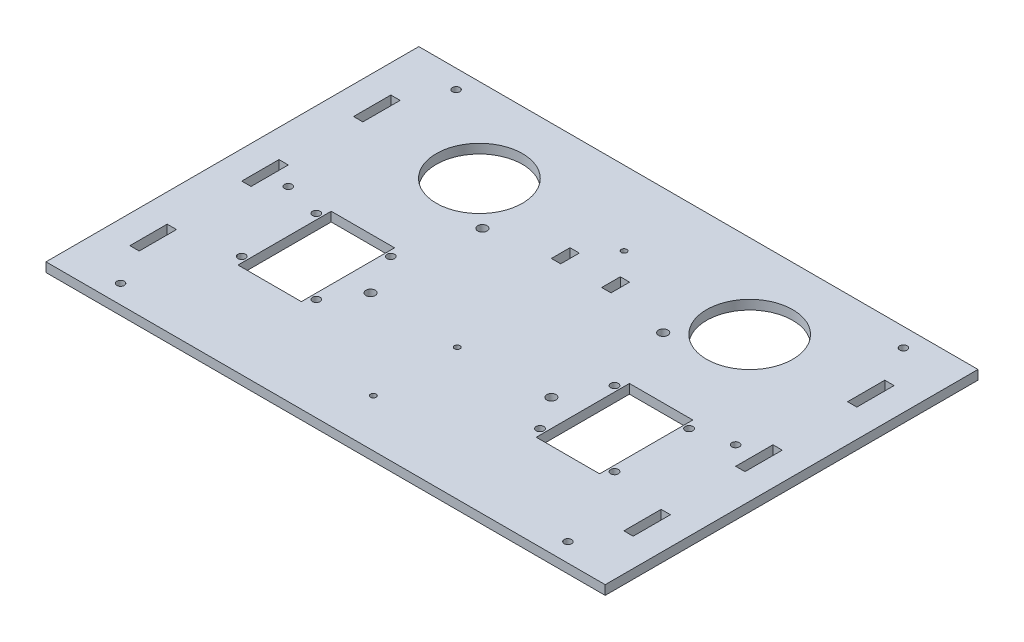
SolidWorks part; units mm, degrees
ref_plane "前基準面" through (0, 0, 0) normal (0, 0, 1) x (1, 0, 0)
ref_plane "上基準面" through (0, 0, 0) normal (0, 1, 0) x (1, 0, 0)
ref_plane "右基準面" through (0, 0, 0) normal (1, 0, 0) x (0, 0, -1)
sketch "草圖1" plane through (0, 0, 0) normal (0, 1, 0) x (1, 0, 0)
  line L0 (-130, 90) -> (130, 90) construction
  line L1 (-150, 100) -> (150, 100)
  line L2 (-150, 100) -> (-150, -100)
  line L3 (-150, -100) -> (150, -100)
  line L5 (0, 100) -> (0, -100) construction
  line L8 (-130, 100) -> (-110, 100) construction
  line L9 (-150, 100) -> (-150, -100) construction
  line L16 (-130, 100) -> (-130, -100) construction
  line L17 (-130, -100) -> (-110, -100) construction
  line L35 (-110, 100) -> (-110, -100) construction
  line L38 (-110, 100) -> (110, 100) construction
  line L41 (-110, 100) -> (-110, 80) construction
  line L50 (-110, 80) -> (110, 80) construction
  line L59 (110, 100) -> (110, 80) construction
  line L65 (-150, -100) -> (150, -100) construction
  line L68 (150, -100) -> (150, 100)
  line L77 (110, 100) -> (130, 100) construction
  line L80 (110, 100) -> (110, -100) construction
  line L83 (110, -100) -> (130, -100) construction
  line L86 (130, 100) -> (130, -100) construction
  line L89 (110, -100) -> (-110, -100) construction
  line L92 (110, -100) -> (110, -80) construction
  line L93 (-150, 100) -> (150, 100) construction
  line L108 (110, -80) -> (-110, -80) construction
  line L109 (-110, -100) -> (-110, -80) construction
  line L110 (130, -70) -> (135, -70)
  line L111 (-120, 100) -> (-120, -100) construction
  line L112 (-130, -90) -> (130, -90) construction
  line L113 (120, -100) -> (120, 100) construction
  line L114 (-130, 70) -> (-135, 70)
  line L115 (-130, 70) -> (-130, 50)
  line L116 (-130, 50) -> (-135, 50)
  line L117 (-135, 70) -> (-135, 50)
  line L118 (-130, 10) -> (-135, 10)
  line L119 (-130, 10) -> (-130, -10)
  line L120 (-130, -10) -> (-135, -10)
  line L121 (-135, 10) -> (-135, -10)
  line L122 (-130, -50) -> (-135, -50)
  line L123 (-130, -50) -> (-130, -70)
  line L124 (-130, -70) -> (-135, -70)
  line L125 (-135, -50) -> (-135, -70)
  line L126 (135, -50) -> (135, -70)
  line L127 (130, -50) -> (135, -50)
  line L128 (130, -50) -> (130, -70)
  line L129 (130, -10) -> (135, -10)
  line L130 (135, 10) -> (135, -10)
  line L131 (130, 10) -> (135, 10)
  line L132 (130, 10) -> (130, -10)
  line L133 (130, 50) -> (135, 50)
  line L134 (135, 70) -> (135, 50)
  line L135 (130, 70) -> (135, 70)
  line L136 (130, 70) -> (130, 50)
  circle A61 centre (-120, 0) radius 2
  circle A62 centre (120, 0) radius 2
  circle A73 centre (-120, 90) radius 2
  circle A74 centre (120, 90) radius 2
  circle A75 centre (120, -90) radius 2
  circle A76 centre (-120, -90) radius 2
  point P6 (0, 0)
  point P9 (0, -80)
  point P24 (-140, 64.2857)
  point P47 (-140, 38.5714)
  point P54 (-140, 12.8571)
  point P61 (-140, -12.8571)
  point P71 (-140, -38.5714)
  point P78 (-140, -64.2857)
  dimension "D3" = 300
  dimension "D5" = 20
  dimension "D8" = 220
  dimension "D13" = 4
  dimension "D14" = 20
  dimension "D2" = 200
  dimension "D4" = 20
  dimension "D6" = 20
  dimension "D7" = 20
  dimension "D9" = 10
  dimension "D10" = 10
  dimension "D11" = 10
  dimension "D12" = 10
  dimension "D15" = 20
  dimension "D16" = 20
  dimension "D17" = 200
  dimension "D18" = 5
  dimension "D19" = 40
  dimension "D20" = 40
  dimension "D21" = 30
  dimension "D23" = 90
  dimension "D22" = 2
extrude "填料-伸長1" add sketch "草圖1" along normal blind 5
sketch "草圖2" plane through (0, 5, 0) normal (0, 1, 0) x (1, 0, 0)
  line L0 (0, 116.4556) -> (0, -113.9778) construction
  line L1 (115, 55) -> (30, 55) construction
  line L2 (-72.5, 97.5) -> (-72.5, 12.5) construction
  line L3 (-115, 55) -> (-30, 55) construction
  line L4 (72.5, 97.5) -> (72.5, 12.5) construction
  line L10 (7.5, -54.8861) -> (-7.5, -54.8861) construction
  line L15 (7.5, -54.8861) -> (7.5, 15.1139) construction
  line L16 (7.5, 15.1139) -> (-7.5, 15.1139) construction
  line L17 (-7.5, -54.8861) -> (-7.5, 15.1139) construction
  line L20 (-7.5, 15.1139) -> (7.5, 15.1139) construction
  line L30 (150, 100) -> (-150, 100) construction
  line L35 (-110, 100) -> (-110, -100) construction
  line L36 (36, -47.3861) -> (-36, -47.3861) construction
  line L37 (36, -47.3861) -> (36, 62.6139) construction
  line L38 (36, 62.6139) -> (-36, 62.6139) construction
  line L39 (-36, -47.3861) -> (-36, 62.6139) construction
  line L40 (-105, 0) -> (-55, 0) construction
  line L41 (-105, 0) -> (-105, -50) construction
  line L42 (-55, 0) -> (-55, -50) construction
  line L43 (-97, 0) -> (-63, 0)
  line L46 (-97, 0) -> (-97, -50)
  line L49 (-97, -50) -> (-63, -50)
  line L60 (-7.5, -7.3861) -> (7.5, -7.3861)
  line L61 (-7.5, -7.3861) -> (-7.5, -32.3861)
  line L62 (-7.5, -32.3861) -> (7.5, -32.3861)
  line L63 (7.5, -7.3861) -> (7.5, -32.3861)
  line L64 (-63, 0) -> (-63, -50)
  line L67 (-105, -50) -> (-55, -50) construction
  line L68 (-7.5, -16.8861) -> (7.5, -16.8861) construction
  line L69 (-7.5, -16.8861) -> (-7.5, -86.8861) construction
  line L70 (-7.5, -86.8861) -> (7.5, -86.8861) construction
  line L71 (7.5, -16.8861) -> (7.5, -86.8861) construction
  line L73 (-150, -100) -> (150, -100) construction
  line L74 (97, 0) -> (97, -50)
  line L75 (240, -52.3861) -> (-240, -52.3861) construction
  line L76 (240, -52.3861) -> (240, 27.6139) construction
  line L78 (-240, -52.3861) -> (-240, 27.6139) construction
  line L83 (0, -40.4951) -> (0, 39.5049) construction
  line L85 (97, -50) -> (63, -50)
  line L86 (63, 0) -> (63, -50)
  line L87 (97, 0) -> (63, 0)
  line L88 (-7.5, -47.3861) -> (-7.5, -72.3861)
  line L89 (-7.5, -47.3861) -> (7.5, -47.3861)
  line L90 (7.5, -47.3861) -> (7.5, -72.3861)
  line L91 (-7.5, -72.3861) -> (7.5, -72.3861)
  line L92 (240, 27.6139) -> (-240, 27.6139) construction
  circle A0 centre (-72.5, 55) radius 42.5
  circle A1 centre (-72.5, 55) radius 22.1
  circle A2 centre (-87, 55) radius 2
  circle A3 centre (-58, 55) radius 2
  circle A4 centre (58, 55) radius 2
  circle A5 centre (87, 55) radius 2
  circle A6 centre (72.5, 55) radius 22.1
  circle A7 centre (72.5, 55) radius 42.5
  circle A11 centre (0, -42.3861) radius 1.25 construction
  circle A12 centre (0, 27.6139) radius 35 construction
  circle A13 centre (0, 2.6139) radius 1.25 construction
  circle A28 centre (60, -45) radius 2.05
  circle A34 centre (0, -29.3861) radius 1.5
  circle A35 centre (0, -74.3861) radius 1.5
  circle A36 centre (-100, -5) radius 2.05
  circle A37 centre (-60, -5) radius 2.05
  circle A38 centre (-100, -45) radius 2.05
  circle A39 centre (-60, -45) radius 2.05
  circle A40 centre (100, -45) radius 2.05
  circle A41 centre (60, -5) radius 2.05
  circle A42 centre (100, -5) radius 2.05
  circle A43 centre (0, -12.3861) radius 35 construction
  point P29 (0, 62.6139)
  point P46 (-7.5, -19.8861)
  point P57 (-7.5, -19.8861)
  point P85 (-96.5, 66.7857)
  point P90 (-141.5, 66.7857)
  point P91 (-140, 13.2857)
  point P92 (-140, 68.2857)
  point P116 (0, -54.8861)
  point P130 (0, -86.8861)
  point P142 (0, -52.3861)
  point P143 (0, 47.6139)
  dimension "D1" = 85
  dimension "D2" = 44.2
  dimension "D4" = 4
  dimension "D8" = 72
  dimension "D10" = 45
  dimension "D7" = 2
  dimension "D16" = 70
  dimension "D13" = 2.5
  dimension "D17" = 2
  dimension "D24" = 45
  dimension "D25" = 4.1
  dimension "D33" = 8
  dimension "D36" = 45
  dimension "D39" = 3
  dimension "D3" = 29
  dimension "D5" = 60
  dimension "D6" = 12.5
  dimension "D9" = 25
  dimension "D11" = 70
  dimension "D12" = 110
  dimension "D14" = 5
  dimension "D15" = 5
  dimension "D18" = 40
  dimension "D19" = 40
  dimension "D20" = 45
  dimension "D21" = 34
  dimension "D23" = 50
  dimension "D26" = 2
  dimension "D27" = 40
  dimension "D29" = 55
  dimension "D30" = 50
  dimension "D31" = 15
  dimension "D32" = 40
  dimension "D34" = 70
  dimension "D35" = 15
  dimension "D37" = 12.5
  dimension "D38" = 32
  dimension "D40" = 5
  dimension "D41" = 5
  dimension "D42" = 50
  dimension "D43" = 80
  dimension "D44" = 480
sketch "草圖3" plane through (0, 5, 0) normal (0, 1, 0) x (1, 0, 0)
  line L0 (0, 200116.4556) -> (0, -200113.9778) construction
  line L1 (0, 200116.4556) -> (0, -200113.9778) construction
  line L3 (-41, 42.6139) -> (-56, 42.6139) construction
  line L4 (-41, 42.6139) -> (-41, 22.6139) construction
  line L5 (-41, 22.6139) -> (-56, 22.6139) construction
  line L6 (-56, 42.6139) -> (-56, 22.6139) construction
  line L7 (0, 0) -> (0, 42.1207) construction
  line L8 (41, 22.6139) -> (56, 22.6139) construction
  line L9 (-7.5, -54.8861) -> (-7.5, 15.1139) construction
  line L10 (7.5, 15.1139) -> (-7.5, 15.1139) construction
  line L11 (7.5, 15.1139) -> (7.5, 25.1139) construction
  line L12 (7.5, 25.1139) -> (-7.5, 25.1139) construction
  line L13 (-7.5, 15.1139) -> (-7.5, 25.1139) construction
  line L14 (41, 42.6139) -> (41, 22.6139) construction
  line L15 (56, 42.6139) -> (56, 22.6139) construction
  line L16 (41, 42.6139) -> (56, 42.6139) construction
  line L17 (-97, -50) -> (-63, -50) construction
  line L18 (-63, 0) -> (-63, -50) construction
  line L19 (-97, 0) -> (-63, 0) construction
  line L20 (-97, 0) -> (-97, -50) construction
  line L21 (-97, -50) -> (-63, -50)
  line L22 (-63, 0) -> (-63, -50)
  line L23 (-97, 0) -> (-63, 0)
  line L24 (-97, 0) -> (-97, -50)
  line L25 (97, 0) -> (97, -50)
  line L26 (97, 0) -> (63, 0)
  line L27 (63, 0) -> (63, -50)
  line L28 (97, -50) -> (63, -50)
  line L29 (36, 62.6139) -> (-36, 62.6139) construction
  line L30 (-11, 67.1139) -> (11, 67.1139) construction
  line L31 (-11, 67.1139) -> (-11, -2.8861) construction
  line L32 (-11, -2.8861) -> (11, -2.8861) construction
  line L33 (11, 67.1139) -> (11, -2.8861) construction
  line L34 (-11, 47.1139) -> (-16, 47.1139)
  line L35 (-11, 47.1139) -> (-11, 37.1139)
  line L36 (-11, 37.1139) -> (-16, 37.1139)
  line L37 (-16, 47.1139) -> (-16, 37.1139)
  line L38 (11, 47.1139) -> (16, 47.1139)
  line L39 (11, 47.1139) -> (11, 37.1139)
  line L40 (11, 37.1139) -> (16, 37.1139)
  line L41 (16, 47.1139) -> (16, 37.1139)
  circle A0 centre (0, -74.3861) radius 1.5 construction
  circle A1 centre (0, -74.3861) radius 1.5
  circle A2 centre (0, -29.3861) radius 1.5 construction
  circle A3 centre (0, -29.3861) radius 1.5
  circle A10 centre (-48.5, 32.6139) radius 2.5
  circle A11 centre (48.5, 32.6139) radius 2.5
  circle A12 centre (48.5, -27.3861) radius 2.5
  circle A13 centre (-48.5, -27.3861) radius 2.5
  circle A14 centre (-72.5, 55) radius 22.1 construction
  circle A15 centre (-72.5, 55) radius 22.1 construction
  circle A16 centre (72.5, 55) radius 22.1 construction
  circle A17 centre (72.5, 55) radius 22.1 construction
  circle A18 centre (-72.5, 55) radius 23.1
  circle A19 centre (72.5, 55) radius 23.1
  circle A20 centre (0, 60.1139) radius 1.5
  circle A21 centre (0, 20.1139) radius 2 construction
  circle A22 centre (-100, -45) radius 2.05 construction
  circle A23 centre (-60, -45) radius 2.05 construction
  circle A24 centre (-60, -5) radius 2.05 construction
  circle A25 centre (-100, -5) radius 2.05 construction
  circle A26 centre (-100, -45) radius 2.05
  circle A27 centre (-60, -45) radius 2.05
  circle A28 centre (-60, -5) radius 2.05
  circle A29 centre (-100, -5) radius 2.05
  circle A30 centre (100, -5) radius 2.05
  circle A31 centre (60, -5) radius 2.05
  circle A32 centre (60, -45) radius 2.05
  circle A33 centre (100, -45) radius 2.05
  point P29 (-56, 32.6139)
  point P32 (-48.5, 22.6139)
  point P62 (-7.5, 20.1139)
  point P64 (0, 67.1139)
  point P95 (-72.5, 60)
  dimension "D2" = 5
  dimension "D8" = 3
  dimension "D11" = 4
  dimension "D3" = 15
  dimension "D4" = 20
  dimension "D5" = 2
  dimension "D6" = 60
  dimension "D9" = 40
  dimension "D10" = 10
  dimension "D12" = 112
  dimension "D13" = 20
  dimension "D14" = 22
  dimension "D15" = 70
  dimension "D16" = 7
  dimension "D17" = 5
  dimension "D18" = 10
  dimension "D19" = 20
  dimension "D7" = 1
extrude "除料-伸長1" cut sketch "草圖3" against normal through all
